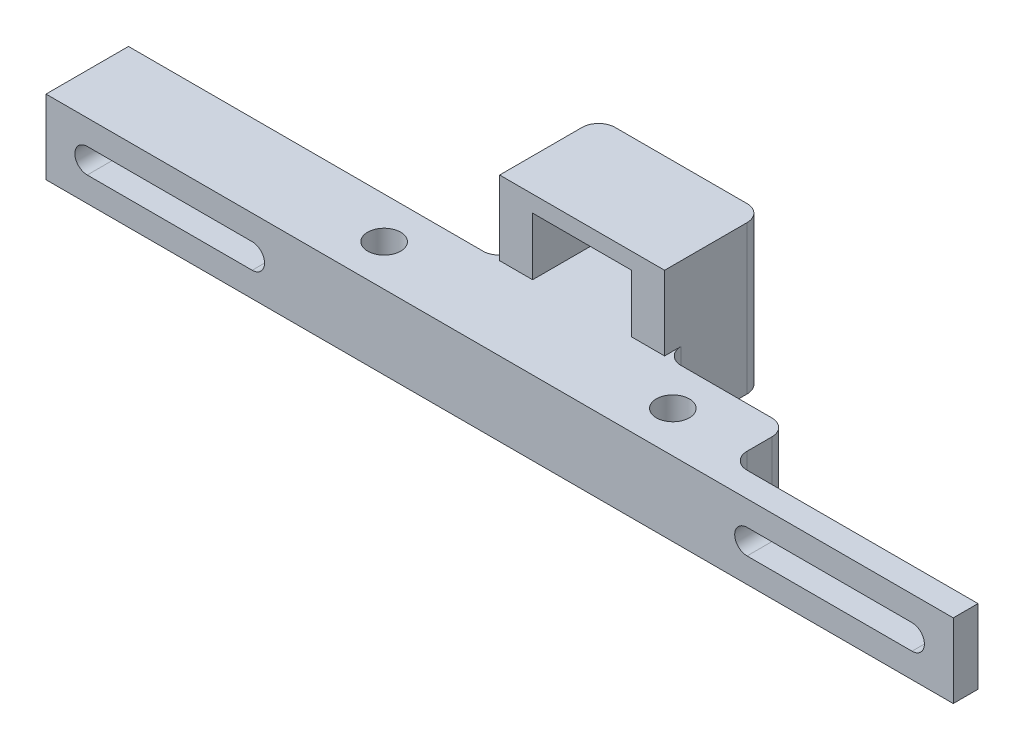
SolidWorks part; units mm, degrees
ref_plane "Plano frontal" through (0, 0, 0) normal (0, 0, 1) x (1, 0, 0)
ref_plane "Plano superior" through (0, 0, 0) normal (0, 1, 0) x (1, 0, 0)
ref_plane "Plano direito" through (0, 0, 0) normal (1, 0, 0) x (0, 0, -1)
sketch "Esboço1" plane through (0, 0, 0) normal (0, 0, 1) x (1, 0, 0)
  line L0 (-6, 4.5) -> (-6, 11.5)
  line L1 (55, -4.5) -> (-55, -4.5)
  line L2 (55, -4.5) -> (55, 4.5)
  line L3 (55, 4.5) -> (-55, 4.5)
  line L4 (-55, -4.5) -> (-55, 4.5)
  line L5 (55, -4.5) -> (-55, 4.5) construction
  line L6 (55, 4.5) -> (-55, -4.5) construction
  line L7 (10, 13.5) -> (-10, 13.5)
  line L8 (10, 13.5) -> (10, 4.5)
  line L9 (10, 4.5) -> (-10, 4.5)
  line L10 (-10, 13.5) -> (-10, 4.5)
  line L11 (10, 13.5) -> (-10, 4.5) construction
  line L12 (10, 4.5) -> (-10, 13.5) construction
  line L13 (6, 4.5) -> (6, 11.5)
  line L14 (-6, 11.5) -> (6, 11.5)
  line L15 (-50, 0) -> (-30, 0) construction
  line L16 (-50, 1.5) -> (-30, 1.5)
  line L17 (-10, 4.5) -> (-10, -4.5)
  line L18 (10, 4.5) -> (10, -4.5)
  line L19 (-50, -1.5) -> (-30, -1.5)
  line L22 (30, 0) -> (50, 0) construction
  line L23 (30, 1.5) -> (50, 1.5)
  line L24 (30, -1.5) -> (50, -1.5)
  arc A0 (-50, 1.5) -> (-50, -1.5) centre (-50, 0) ccw
  arc A1 (-30, -1.5) -> (-30, 1.5) centre (-30, 0) ccw
  arc A2 (30, 1.5) -> (30, -1.5) centre (30, 0) ccw
  arc A3 (50, -1.5) -> (50, 1.5) centre (50, 0) ccw
  point P0 (0, 0)
  point P6 (0, 9)
  point P15 (-40, 0)
  point P26 (40, 0)
  dimension "D3" = 5
  dimension "D1" = 4
  dimension "D2" = 4
  dimension "D4" = 5
extrude "Ressalto-extrusão2" add sketch "Esboço1" along normal blind 10 contours L3 L18 L1 L2 A3 L24 A2 L23 | L18 L3 L9 L17 L1 | L17 L3 L4 L1 A1 L19 A0 L16 region at (0, 0, 0) region at (-10.4589, 0, 0) region at (32.5, 4.0411, 0)
extrude "Ressalto-extrusão3" add sketch "Esboço1<5>" against normal blind 12 contours L18 L3 L9 L17 L1 | L0 L14 L13 L3 L8 L7 L10 region at (-8, 4.7193, 0) region at (0, 0, 0)
sketch "Esboço1<5>" plane through (0, 0, 0) normal (0, 0, 1) x (1, 0, 0) same geometry as "Esboço1"
sketch "Esboço2" plane through (0, 4.5, 0) normal (0, 1, 0) x (1, 0, 0)
  line L0 (-55, -10) -> (-55, 0) construction
  line L1 (55, 0) -> (25, 0)
  line L2 (55, 0) -> (55, -7)
  line L3 (55, -7) -> (25, -7)
  line L4 (25, 0) -> (25, -7)
  circle A0 centre (-19, -5) radius 2
  circle A1 centre (16, -5) radius 2
  point P10 (-55, -5)
  point P12 (0, 0)
  dimension "D1" = 4
  dimension "D2" = 36
  dimension "D3" = 35
extrude "Corte-extrusão4" cut sketch "Esboço2" against normal up to surface (9 mm away) up to face at (5.625, -4.5, -2)
fillet "Filete2" radius 2 6 edges at (25, 0, 7) (25, 0, 0) (10, 4.5, -12) (-10, 4.5, -12)
